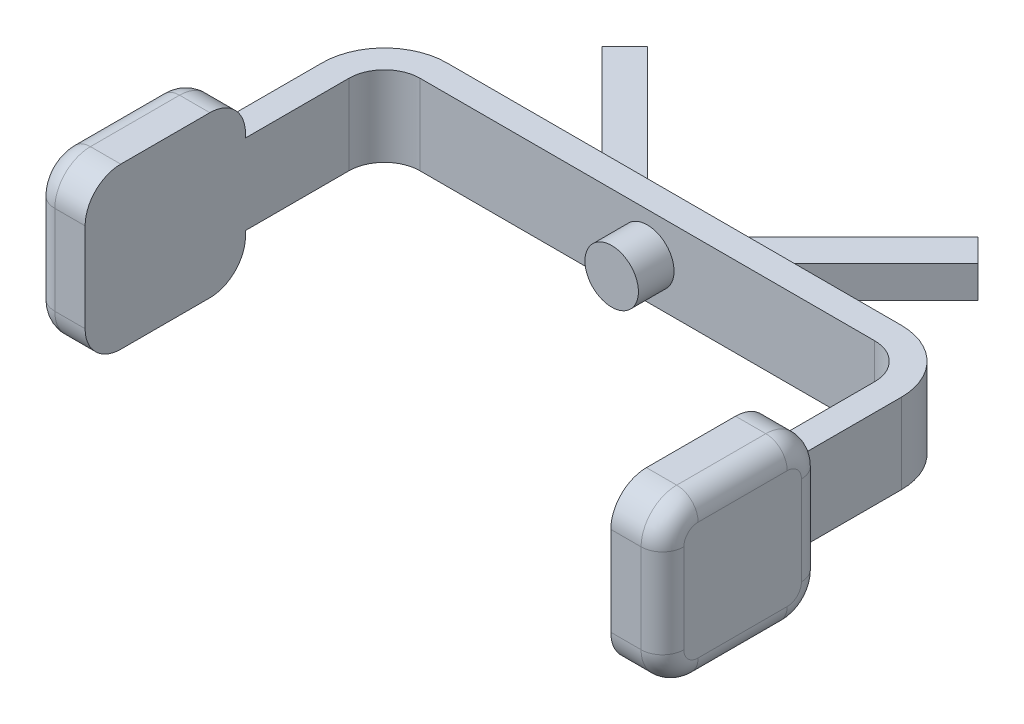
SolidWorks part; units mm, degrees
ref_plane "前视基准面" through (0, 0, 0) normal (0, 0, 1) x (1, 0, 0)
ref_plane "上视基准面" through (0, 0, 0) normal (0, 1, 0) x (1, 0, 0)
ref_plane "右视基准面" through (0, 0, 0) normal (1, 0, 0) x (0, 0, -1)
sketch "草图1" plane through (0, 0, 0) normal (0, 1, 0) x (1, 0, 0)
  line L0 (-1.5, 0) -> (1.5, 0)
  line L1 (1.5, 0) -> (9.2782, 7.7782)
  line L2 (-1.5, 0) -> (-9.2782, 7.7782)
  line L3 (-9.2782, 7.7782) -> (-10.551, 6.5054)
  line L4 (9.2782, 7.7782) -> (10.551, 6.5054)
  line L5 (-12.75, -1.5) -> (12.75, -1.5)
  line L6 (-3.35, -1.5) -> (3.35, -1.5) construction
  line L7 (-14.75, -3.5) -> (-14.75, -9.3)
  line L8 (14.75, -3.5) -> (14.75, -9.3)
  line L9 (-10.551, 6.5054) -> (-4.0456, 0)
  line L10 (10.551, 6.5054) -> (4.0456, 0)
  line L11 (-16.25, -3.5) -> (-16.25, -9.3)
  line L12 (-12.75, 0) -> (12.75, 0)
  line L13 (16.25, -3.5) -> (16.25, -9.3)
  line L14 (-16.25, -9.3) -> (-14.75, -9.3)
  line L15 (14.75, -9.3) -> (16.25, -9.3)
  arc A0 (-12.75, -1.5) -> (-14.75, -3.5) centre (-12.75, -3.5) ccw
  arc A1 (14.75, -3.5) -> (12.75, -1.5) centre (12.75, -3.5) ccw
  arc A2 (-12.75, 0) -> (-16.25, -3.5) centre (-12.75, -3.5) ccw
  arc A3 (16.25, -3.5) -> (12.75, 0) centre (12.75, -3.5) ccw
  point P4 (0, 0)
  point P8 (0, 0)
  point P11 (0, 1.5)
  point P14 (0, 0)
  point P16 (0, -1.5)
  point P20 (0, 0)
  point P22 (-14.75, -1.5)
  point P25 (14.75, -1.5)
  point P35 (0, 0)
  point P36 (0, 0)
  point P37 (0, 0)
  point P39 (1.5, 0)
  dimension "D2" = 2
  dimension "D3" = 2
  dimension "D1" = 29.5
  dimension "D5" = 5.8
  dimension "D6" = 0
  dimension "D7" = 11
  dimension "D8" = 11
  dimension "D9" = 5.8
  dimension "D4" = 1.5
extrude "凸台-拉伸2" add sketch "草图1" along normal mid plane 4.5 contours L12 A3 L13 L15 L8 A1 L5 A0 L7 L14 L11 A2
extrude "凸台-拉伸4" add sketch "草图1<6>" along normal mid plane 1.8 contours L1 L12 L10 L4 | L9 L12 L2 L3 region at (-6.3153, 0, -3.5803) region at (6.3153, 0, -3.5803)
sketch "草图1<6>" plane through (0, 0, 0) normal (0, 1, 0) x (1, 0, 0) same geometry as "草图1"
ref_plane "基准面1" through (14.75, 0, 0) normal (-1, 0, 0) x (0, 0, 1)
sketch "草图2" plane through (14.75, 0, 0) normal (-1, 0, 0) x (0, 0, 1)
  line L0 (9.3, 2.25) -> (9.3, -2.25) construction
  line L1 (9.3, 0) -> (13.8, -0.0211) construction
  line L2 (9.3, 2.25) -> (9.3, -2.25) construction
  line L3 (16.3, 4.4789) -> (11.3, 4.4789)
  line L4 (18.3, 2.4789) -> (18.3, -2.5211)
  line L5 (16.3, -4.5211) -> (11.3, -4.5211)
  line L6 (9.3, 2.4789) -> (9.3, -2.5211)
  line L7 (18.3, 4.4789) -> (9.3, -4.5211) construction
  line L8 (18.3, -4.5211) -> (9.3, 4.4789) construction
  arc A0 (11.3, 4.4789) -> (9.3, 2.4789) centre (11.3, 2.4789) ccw
  arc A1 (18.3, -2.5211) -> (16.3, -4.5211) centre (16.3, -2.5211) cw
  arc A2 (11.3, -4.5211) -> (9.3, -2.5211) centre (11.3, -2.5211) cw
  arc A3 (18.3, 2.4789) -> (16.3, 4.4789) centre (16.3, 2.4789) ccw
  dimension "D3" = 2
  dimension "D4" = 2
  dimension "D1" = 9
  dimension "D2" = 9
  dimension "D5" = 0
extrude "凸台-拉伸5" add sketch "草图2" against normal blind 2.9
fillet "圆角1" radius 1.2 8 edges at (17.65, -0.0211, 9.3) (17.65, -3.9353, 9.8858) (17.65, -4.5211, 13.8) (17.65, -3.9353, 17.7142) (17.65, -0.0211, 18.3) (17.65, 3.8931, 17.7142) (17.65, 4.4789, 13.8) (17.65, 3.8931, 9.8858)
mirror "镜向2" about plane through (0, 0, 0) normal (1, 0, 0) of "凸台-拉伸5", "圆角1"
sketch "草图3" plane through (0, 0, 1.5) normal (0, 0, 1) x (1, 0, 0)
  circle A0 centre (0, 0) radius 1.5
extrude "凸台-拉伸6" add sketch "草图3" along normal blind 2
